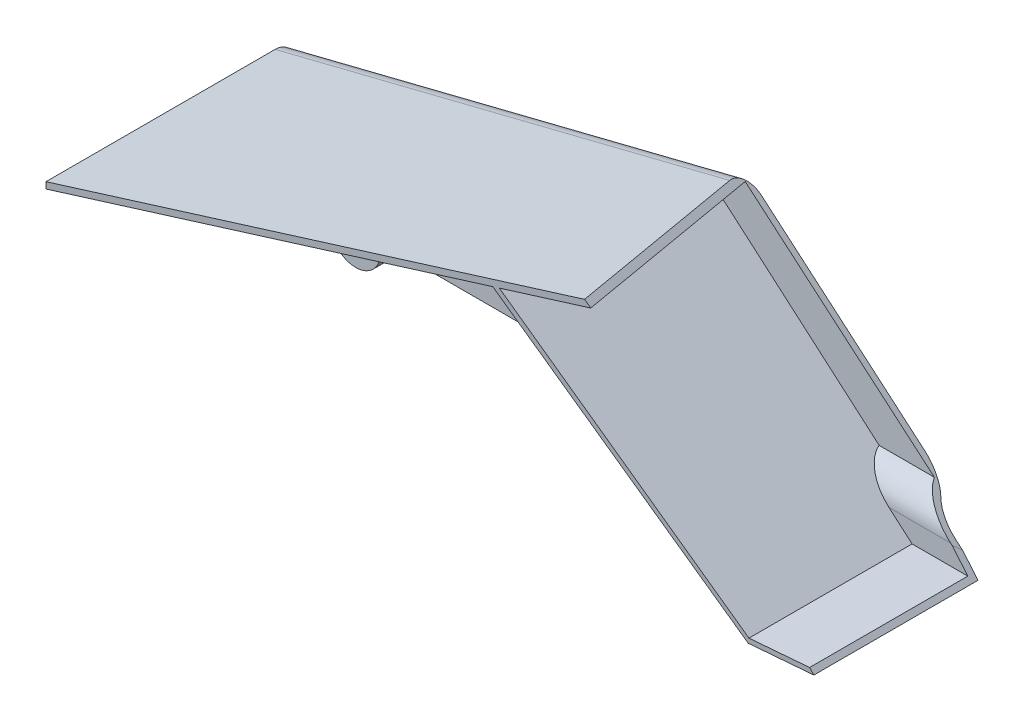
SolidWorks part; units mm, degrees
material "ABS PC"
ref_plane "Piano frontale" through (0, 0, 0) normal (0, 0, 1) x (1, 0, 0)
ref_plane "Piano superiore" through (0, 0, 0) normal (0, 1, 0) x (1, 0, 0)
ref_plane "Piano destro" through (0, 0, 0) normal (1, 0, 0) x (0, 0, -1)
sketch "Schizzo1" plane through (0, 0, 0) normal (0, 0, 1) x (1, 0, 0)
  line L0 (-49, 0) -> (49, 0)
  line L1 (-49, 0) -> (-49, 5)
  line L2 (-49, 5) -> (-65, 5)
  line L3 (-65, 5) -> (-65, 17)
  line L4 (-65, 17) -> (17.4553, 37.6429)
  line L5 (17.4553, 37.6429) -> (49, 0)
  point P4 (0, 0)
  point P8 (2.9043, 34)
  dimension "D1" = 98
  dimension "D2" = 5
  dimension "D3" = 16
  dimension "D4" = 12
  dimension "D5" = 85
  dimension "D6" = 70
  dimension "D7" = 34
extrude "Estrusione-Estrusione1" add sketch "Schizzo1" along normal blind 40
sketch "Schizzo3" plane through (0, 0, 0) normal (1, 0, 0) x (0, 0, -1)
  line L0 (-3.5, 4) -> (-3.5, 0)
  line L1 (-40, 0) -> (0, 0) construction
  line L2 (-3.5, 0) -> (0, 0)
  line L3 (0, 0) -> (0, 0.5)
  line L4 (0, 0.5) -> (0, 7.5)
  arc A0 (0, 7.5) -> (-3.5, 4) centre (0, 4) ccw
  dimension "D1" = 7
  dimension "D2" = 4
extrude "Taglio-Estrusione1" cut sketch "Schizzo3" against normal through all both and the other way through all
shell "Svuota1" thickness 1 removed face at (0, 0, 21.75) removed face at (-49, 2.8011, 18.0781) removed face at (-57, 5, 21.6771) removed face at (-65, 10.4112, 16.7537) removed face at (-26.9241, 10.7738, 40) removed face at (36.7777, 14.5851, 14.6208)
sketch "Schizzo5" plane through (0, 0, 0) normal (0, 0, 1) x (1, 0, 0)
  line L0 (1.3224, 32.5731) -> (2.2925, 32.816)
  line L1 (18.1693, 36.7908) -> (-65, 15.9691) construction
  line L2 (2.2925, 32.816) -> (39.3577, 0.7665)
  line L3 (39.3577, 0.7665) -> (48.3577, 0.7665)
  line L4 (49, 0) -> (45.648, 4) construction
  line L5 (48.3577, 0.7665) -> (49, 0)
  line L6 (49, 0) -> (39.2565, 0)
  line L7 (-49, 0) -> (49, 0) construction
  line L8 (39.2565, 0) -> (1.3224, 32.5731)
  dimension "D1" = 1
  dimension "D2" = 1
  dimension "D3" = 49
  dimension "D4" = 50
  dimension "D5" = 9
extrude "Estrusione-Estrusione2" add sketch "Schizzo5" against normal up to body from surface separate body starting at face at (-23.5938, 26.8507, 40)
sketch "Schizzo8" plane through (0, 0, 0) normal (0, 0, 1) x (1, 0, 0)
  line L0 (-49, 4) -> (-49, 0) construction
  line L1 (-49, 0) -> (39.2565, 0) construction
  circle A0 centre (-45, 4) radius 4
  circle A1 centre (9, 4) radius 4
  dimension "D1" = 8
  dimension "D2" = 54
extrude "Estrusione-Estrusione3" add sketch "Schizzo8" against normal up to body from offset 10 separate body
sketch "Schizzo9" plane through (0, 0, 0) normal (0, 0, 1) x (1, 0, 0)
  circle A0 centre (-45, 4) radius 1.5
  circle A1 centre (9, 4) radius 1.5
  arc A2 (-49, 4) -> (-45, 0) centre (-45, 4) ccw construction
  dimension "D1" = 3
extrude "Taglio-Estrusione2" cut sketch "Schizzo9" against normal blind 30 from surface starting at face at (-41, 4, 10)
ref_plane "Piano1" through (-7.8386, 31.3105, 0) normal (-0.2429, 0.9701, 0) x (0.9701, 0.2429, 0)
sketch "Schizzo13" plane through (-7.8386, 31.3105, 0) normal (-0.2429, 0.9701, 0) x (0.9701, 0.2429, 0)
  line L1 (26.0745, 0) -> (-58.9255, 0) construction
  line L2 (16.0745, 0) -> (26.0745, 0)
  line L3 (26.0745, 0) -> (26.0745, -40)
  line L4 (26.0745, -40) -> (25.0745, -40)
  line L5 (26.0745, -40) -> (-58.9255, -40) construction
  line L6 (25.0745, -40) -> (16.0745, 0)
  dimension "D1" = 10
  dimension "D2" = 1
sketch "Schizzo17" plane through (0, 0, 0) normal (0, 0, 1) x (1, 0, 0)
  line L0 (7.7547, 35.2143) -> (60.9911, -10.2377)
  line L8 (17.4553, 37.6429) -> (-65, 17) construction
  dimension "D1" = 10
  dimension "D2" = 70
sweep "Taglia-Sweep3" cut profiles "Schizzo13" path "Schizzo17"
sketch "Schizzo18" plane through (0, 0, 0) normal (0, 1, 0) x (1, 0, 0)
  line L1 (-1, -3) -> (-12, -3)
  line L2 (-1, -3) -> (-1, -4)
  line L3 (-1, -4) -> (-12, -4)
  line L4 (-12, -3) -> (-12, -4)
  line L5 (5, -4.5) -> (5, -10) construction
  line L6 (-45, -4.5) -> (9, -4.5) construction
  point P6 (-1, -3.5)
  dimension "D1" = 1
  dimension "D2" = 11
  dimension "D3" = 6
  dimension "D4" = 0.5
extrude "Taglio-Estrusione3" cut sketch "Schizzo18" along normal blind 5
fillet "Raccordo1" radius 2 1 edges at (16.952, 37.0014, 40) type face fillet first side face at (31.2304, 17.569, 9.9493) second side face at (8.3491, 17.3894, 40)
fillet "Raccordo2" radius 3 1 edges at (-28.6227, 26.1071, 0) type face fillet first side face at (-18.398, 28.6669, 23.62) second side face at (-20.5075, 16.8036, 0)
fillet "Raccordo3" radius 4 1 edges at (-12.3923, 7.5, 0)
sketch "Schizzo22" plane through (0, 0, 0) normal (0, 1, 0) x (1, 0, 0)
  line L0 (-65, -40) -> (49, -30)
  line L1 (49, -40) -> (49, -3.5) construction
  line L2 (49, -30) -> (49, -40)
  line L4 (13.6272, -40) -> (49, -40)
  line L5 (13.6272, -40) -> (-65, -40) construction
  line L6 (13.6272, -40) -> (-65, -40)
  dimension "D2" = 10
extrude "Taglio-Estrusione4" cut sketch "Schizzo22" against normal blind 10 and the other way through all
